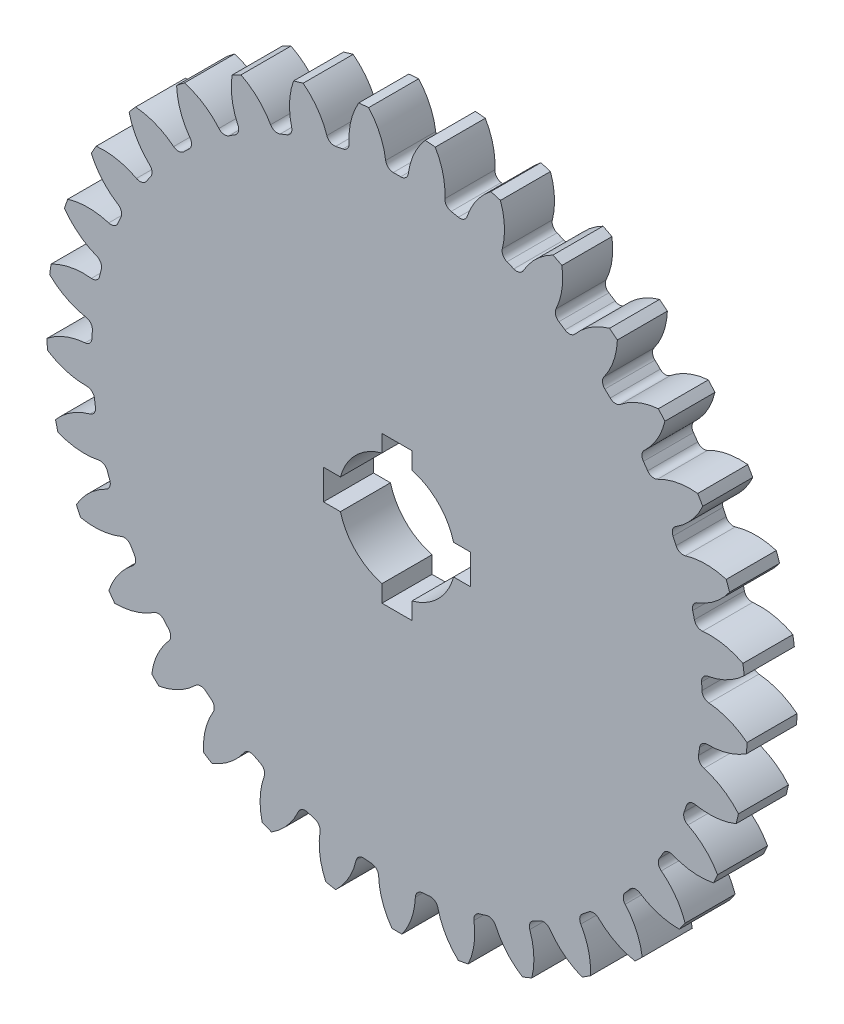
SolidWorks part; units mm, degrees
ref_plane "Front Plane" through (0, 0, 0) normal (0, 0, 1) x (1, 0, 0)
ref_plane "Top Plane" through (0, 0, 0) normal (0, 1, 0) x (1, 0, 0)
ref_plane "Right Plane" through (0, 0, 0) normal (1, 0, 0) x (0, 0, -1)
sketch "Sketch1" plane through (0, 0, 0) normal (0, 0, 1) x (1, 0, 0)
  line L4 (-1.075, 30.481) -> (0, 0) construction
  line L5 (0, 0) -> (0, 35) construction
  line L6 (0, 0) -> (3.327, 34.8415) construction
  line L7 (-1.6208, 32.9602) -> (0.784, 33.9718) construction
  line L8 (-1.6208, 32.9602) -> (0.4019, 33.0596) construction
  line L11 (1.6208, 32.9602) -> (-1.6208, 32.9602) construction
  circle A0 centre (0, 0) radius 30.5
  circle A1 centre (0, 0) radius 33 construction
  circle A2 centre (0, 0) radius 35
  arc A3 (-2.8289, 34.8855) -> (-1.075, 30.481) centre (-8.1051, 30.2331) cw
  arc A4 (2.8289, 34.8855) -> (1.075, 30.481) centre (8.1051, 30.2331) ccw
  point P5 (-33, 0)
  point P6 (-35, 0)
  point P7 (-30.5, 0)
  point P12 (-1.6208, 32.9602)
  point P22 (1.6208, 32.9602)
  dimension "D5" = 66
  dimension "D1" = 2.5
  dimension "D2" = 2
  dimension "D3" = 20
  dimension "D4" = 3.2416
  dimension "D6" = 5.455
  dimension "D7" = 0.5
extrude "Boss-Extrude1" add sketch "Sketch1" against normal blind 5 contours A2
extrude "Cut-Extrude1" cut sketch "Sketch1<4>" against normal blind 10 contours A4 A2 A3 A0 region at (0, 33.1199, 0)
sketch "Sketch1<4>" plane through (0, 0, 0) normal (0, 0, 1) x (1, 0, 0) same geometry as "Sketch1"
fillet "Fillet2" radius 0.76 2 edges at (1.075, 30.481, -2.5) (-1.075, 30.481, -2.5)
ref_axis "Axis1" through (0, 0, 0) along (0, 0, 1)
pattern_circular "CirPattern2" count 33 over 360 about axis through (0, 0, 0) along (0, 0, 1) of "Cut-Extrude1", "Fillet2"
sketch "Sketch2" plane through (0, 0, 0) normal (0, 0, 1) x (1, 0, 0)
  line L0 (-1.5, 5.6528) -> (-1.5, 7.3485)
  line L1 (-1.5, 4.3485) -> (1.5, 4.3485) construction
  line L2 (-1.5, 4.3485) -> (-1.5, 7.3485) construction
  line L3 (-1.5, 7.3485) -> (1.5, 7.3485) construction
  line L4 (1.5, 4.3485) -> (1.5, 7.3485) construction
  line L5 (-1.5, 4.3485) -> (1.5, 7.3485) construction
  line L6 (-1.5, 7.3485) -> (1.5, 4.3485) construction
  line L7 (4.3485, -1.5) -> (7.3485, -1.5) construction
  line L8 (4.3485, -1.5) -> (4.3485, 1.5) construction
  line L9 (4.3485, 1.5) -> (7.3485, 1.5) construction
  line L10 (7.3485, -1.5) -> (7.3485, 1.5) construction
  line L11 (4.3485, -1.5) -> (7.3485, 1.5) construction
  line L12 (4.3485, 1.5) -> (7.3485, -1.5) construction
  line L13 (-1.5, -7.3485) -> (1.5, -7.3485) construction
  line L14 (-1.5, -7.3485) -> (-1.5, -4.3485) construction
  line L15 (-1.5, -4.3485) -> (1.5, -4.3485) construction
  line L16 (1.5, -7.3485) -> (1.5, -4.3485) construction
  line L17 (-1.5, -7.3485) -> (1.5, -4.3485) construction
  line L18 (-1.5, -4.3485) -> (1.5, -7.3485) construction
  line L19 (-7.3485, -1.5) -> (-4.3485, -1.5) construction
  line L20 (-7.3485, -1.5) -> (-7.3485, 1.5) construction
  line L21 (-7.3485, 1.5) -> (-4.3485, 1.5) construction
  line L22 (-4.3485, -1.5) -> (-4.3485, 1.5) construction
  line L23 (-7.3485, -1.5) -> (-4.3485, 1.5) construction
  line L24 (-7.3485, 1.5) -> (-4.3485, -1.5) construction
  line L25 (-1.5, 7.3485) -> (1.5, 7.3485)
  line L26 (1.5, 7.3485) -> (1.5, 5.6528)
  line L27 (5.6528, 1.5) -> (7.3485, 1.5)
  line L28 (7.3485, 1.5) -> (7.3485, -1.5)
  line L29 (7.3485, -1.5) -> (5.6528, -1.5)
  line L30 (1.5, -7.3485) -> (1.5, -5.6528)
  line L31 (1.5, -7.3485) -> (-1.5, -7.3485)
  line L32 (-1.5, -7.3485) -> (-1.5, -5.6528)
  line L33 (-5.6528, -1.5) -> (-7.3485, -1.5)
  line L34 (-7.3485, -1.5) -> (-7.3485, 1.5)
  line L35 (-7.3485, 1.5) -> (-5.6528, 1.5)
  circle A0 centre (0, 0) radius 7.5 construction
  arc A1 (-1.5, 5.6528) -> (-5.6528, 1.5) centre (0, 0) ccw
  arc A2 (5.6528, 1.5) -> (1.5, 5.6528) centre (0, 0) ccw
  arc A3 (1.5, -5.6528) -> (5.6528, -1.5) centre (0, 0) ccw
  arc A4 (-5.6528, -1.5) -> (-1.5, -5.6528) centre (0, 0) ccw
  point P3 (0, 5.8485)
  point P8 (5.8485, 0)
  point P13 (0, -5.8485)
  point P18 (-5.8485, 0)
  dimension "D1" = 15
  dimension "D2" = 3
extrude "Cut-Extrude2" cut sketch "Sketch2" against normal up to surface (5 mm away) up to face at (0, 0, -5)
equation "\"backlash\"= 0.1mm"
equation "\"module\"= 2mm"
equation "\"pressureAngle\"= 20deg"
equation "\"width\"= 10mm"
equation "\"D1@Sketch1\"= 1.25 * \"module\""
equation "\"D2@Sketch1\"=\"module\""
equation "\"D5@Sketch1\"=\"module\"*\"numberOfTeeth\""
equation "\"D1@Boss-Extrude1\"=\"width\"-5"
equation "\"D3@Sketch1\"=\"pressureAngle\""
equation "\"D1@Cut-Extrude1\"=\"width\""
equation "\"D1@CirPattern2\"=\"numberOfTeeth\""
equation "\"D1@Fillet2\"=0.38*\"module\""
equation "\"D4@Sketch1\"=pi*\"module\"/2+\"backlash\""
equation "\"numberOfTeeth\"= 33"
equation "\"D6@Sketch1\"=180/\"numberOfTeeth\""
equation "\"toothTipProfile\"= 1mm"
equation "\"D7@Sketch1\"=\"toothTipProfile\"/2"
equation "\"lengthOverallRack\"= pi * \"module\" * \"numberOfTeethRack\""
equation "\"numberOfTeethRack\"= 20"
